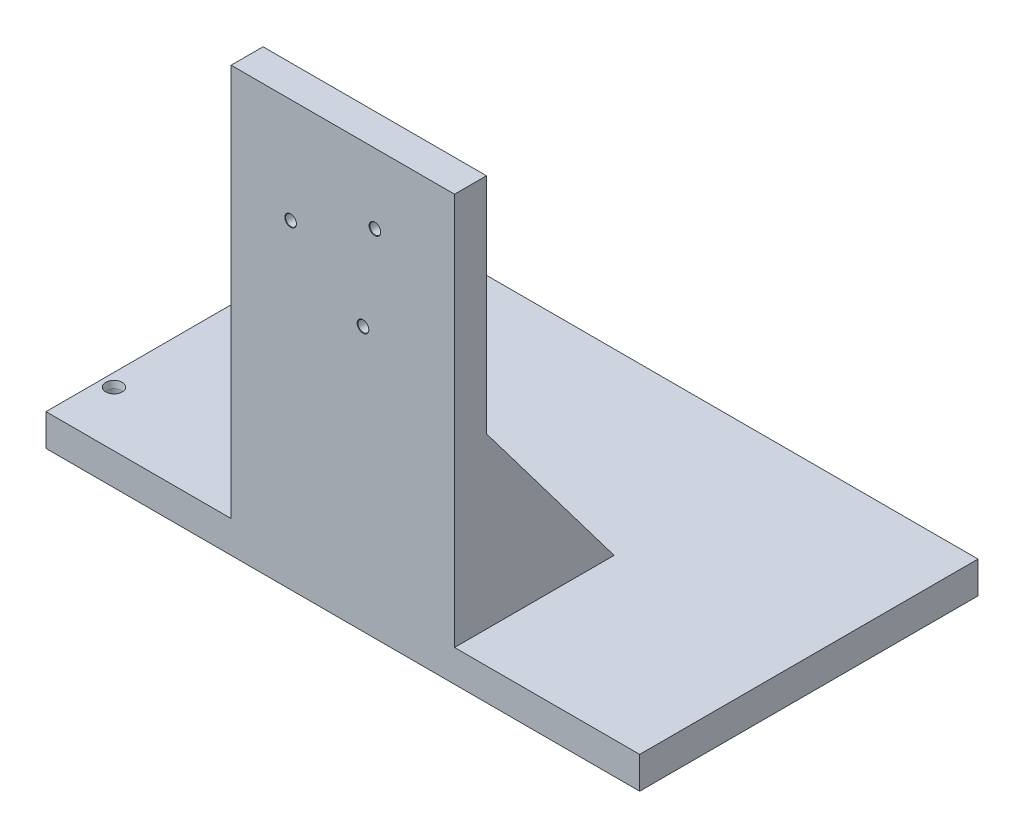
SolidWorks part; units mm, degrees
ref_plane "Front Plane" through (0, 0, 0) normal (0, 0, 1) x (1, 0, 0)
ref_plane "Top Plane" through (0, 0, 0) normal (0, 1, 0) x (1, 0, 0)
ref_plane "Right Plane" through (0, 0, 0) normal (1, 0, 0) x (0, 0, -1)
sketch "Sketch1" plane through (0, 0, 0) normal (0, 0, 1) x (1, 0, 0)
  line L1 (-35, -35) -> (35, -35)
  line L2 (-35, -35) -> (-35, 35)
  line L3 (-35, 35) -> (35, 35)
  line L4 (35, -35) -> (35, 35)
  line L5 (-35, -35) -> (35, 35) construction
  line L6 (-35, 35) -> (35, -35) construction
  point P0 (0, 0)
  dimension "D2" = 70
  dimension "D1" = 70
extrude "Boss-Extrude1" add sketch "Sketch1" along normal blind 10
sketch "Sketch2" plane through (0, 0, 10) normal (0, 0, 1) x (1, 0, 0)
  line L0 (0, 26.65) -> (0, -26.65) construction
  line L5 (-35, 35) -> (35, -35) construction
  line L6 (35, 35) -> (-35, -35) construction
  line L7 (-26.65, 0) -> (26.65, 0) construction
  line L8 (-16.3588, 2.1537) -> (0, 0) construction
  line L9 (10.0446, 13.0903) -> (0, 0) construction
  line L10 (0, 0) -> (6.3143, -15.244) construction
  line L11 (-27, 0) -> (0, 0) construction
  line L12 (0, 0) -> (27, 0) construction
  circle A0 centre (0, 0) radius 26.65 construction
  circle A1 centre (0, 0) radius 16.5 construction
  circle A2 centre (-27, 0) radius 1
  circle A3 centre (27, 0) radius 1
  point P8 (10.0446, 13.0903)
  point P9 (6.3143, -15.244)
  point P10 (-16.3588, 2.1537)
  dimension "D2" = 53.3
  dimension "D3" = 33
  dimension "D6" = 2
  dimension "D1" = 22.5
  dimension "D4" = 120
  dimension "D5" = 120
  dimension "D7" = 27
sketch "Sketch5" plane through (0, 0, 10) normal (0, 0, 1) x (1, 0, 0)
  point P0 (6.3143, -15.244)
  point P3 (10.0446, 13.0903)
  point P6 (-16.3588, 2.1537)
hole_wizard "M3 Clearance Hole1" positions "Sketch5" profile "Sketch4" hole size "M3" standard "ANSI Metric" end condition up to next
sketch "Sketch4" plane through (6.3143, -15.244, 10) normal (1, 0, 0) x (0, -1, 0)
  line L0 (0, 0) -> (0, 10)
  line L1 (0, 10) -> (1.7, 10)
  line L2 (1.7, 10) -> (1.7, 0.125)
  line L3 (1.7, 0.125) -> (1.825, 0)
  line L5 (1.825, 0) -> (0, 0)
  line L6 (-1.7, 0.125) -> (-1.825, 0) construction
  line L11 (0, -6.35) -> (0, 107.95) construction
  dimension "Thru Hole Dia." = 3.4
  dimension "Thru Hole Depth" = 10
  dimension "Near C'Sink Dia." = 3.65
  dimension "Near C'Sink Angle" = 90
sketch "Sketch14" plane through (0, -35, 0) normal (0, -1, 0) x (1, 0, 0)
  line L1 (-35, 10) -> (35, 10)
  line L2 (-35, 10) -> (-35, 0)
  line L3 (-35, 0) -> (35, 0)
  line L4 (35, 10) -> (35, 0)
extrude "Boss-Extrude2" add sketch "Sketch14" along normal blind 63
sketch "Sketch13" plane through (0, -98, 0) normal (0, -1, 0) x (1, 0, 0)
  line L1 (-93, 10) -> (93, 10)
  line L2 (-93, 10) -> (-93, -96)
  line L3 (-93, -96) -> (93, -96)
  line L4 (93, 10) -> (93, -96)
  line L5 (35, 10) -> (-35, 10) construction
  point P5 (0, 10)
  dimension "D1" = 186
  dimension "D2" = 106
extrude "Boss-Extrude3" add sketch "Sketch13" against normal blind 10 contours L3 L4 L1 L2
chamfer "Chamfer1" distance 40 distance2 53 1 edges at (0, -88, 0) first distance on face at (0, -88, -19)
sketch "Sketch17" plane through (0, -88, 0) normal (0, 1, 0) x (1, 0, 0)
  line L0 (-89, 82.2) -> (-89, 7.3) construction
  line L4 (-93, -10) -> (-35, -10) construction
  line L5 (-93, -10) -> (-93, 96) construction
  point P0 (-89, 7.3)
  point P2 (-89, 82.2)
  point P6 (-40.8, 6)
  point P8 (-73.8, 58.1)
  point P10 (-45.9, 58.1)
  point P23 (-41.8329, -3.5201)
  point P24 (0, 0)
  point P25 (0, 0)
  point P26 (0, 0)
  point P29 (-37.4297, 6)
  dimension "D1" = 74.9
  dimension "D2" = 1.3
  dimension "D3" = 15.2
  dimension "D4" = 50.8
  dimension "D5" = 16
  dimension "D6" = 27.9
  dimension "D7" = 5.1
  dimension "D8" = 4
hole_wizard "Hole1" positions "Sketch17" profile "Sketch16" legacy
sketch "Sketch16" plane through (-89, -88, -7.3) normal (1, 0, 0) x (0, 0, 1)
  line L0 (0, 0) -> (0, 9)
  line L1 (0, 9) -> (2.25, 9)
  line L2 (2.25, 9) -> (2.25, 2)
  line L3 (2.25, 2) -> (2.6, 2)
  line L4 (2.6, 2) -> (2.6, 0)
  line L5 (2.6, 0) -> (0, 0)
  line L6 (0, 110) -> (0, -10) construction
  dimension "Diameter" = 4.5
  dimension "Depth" = 9
  dimension "C-Bore Diameter" = 5.2
  dimension "C-Bore Depth" = 2
chamfer "Chamfer2" distance 2 distance2 0.35 5 edges at (-89, -90, -79.6) (-40.8, -90, -3.4) (-89, -90, -4.7) (-73.8, -90, -55.5) (-45.9, -90, -55.5) first distance on face at (-89, -90, -79.6) first distance on face at (-40.8, -90, -3.4) first distance on face at (-89, -90, -4.7) first distance on face at (-73.8, -90, -55.5) first distance on face at (-45.9, -90, -55.5)
